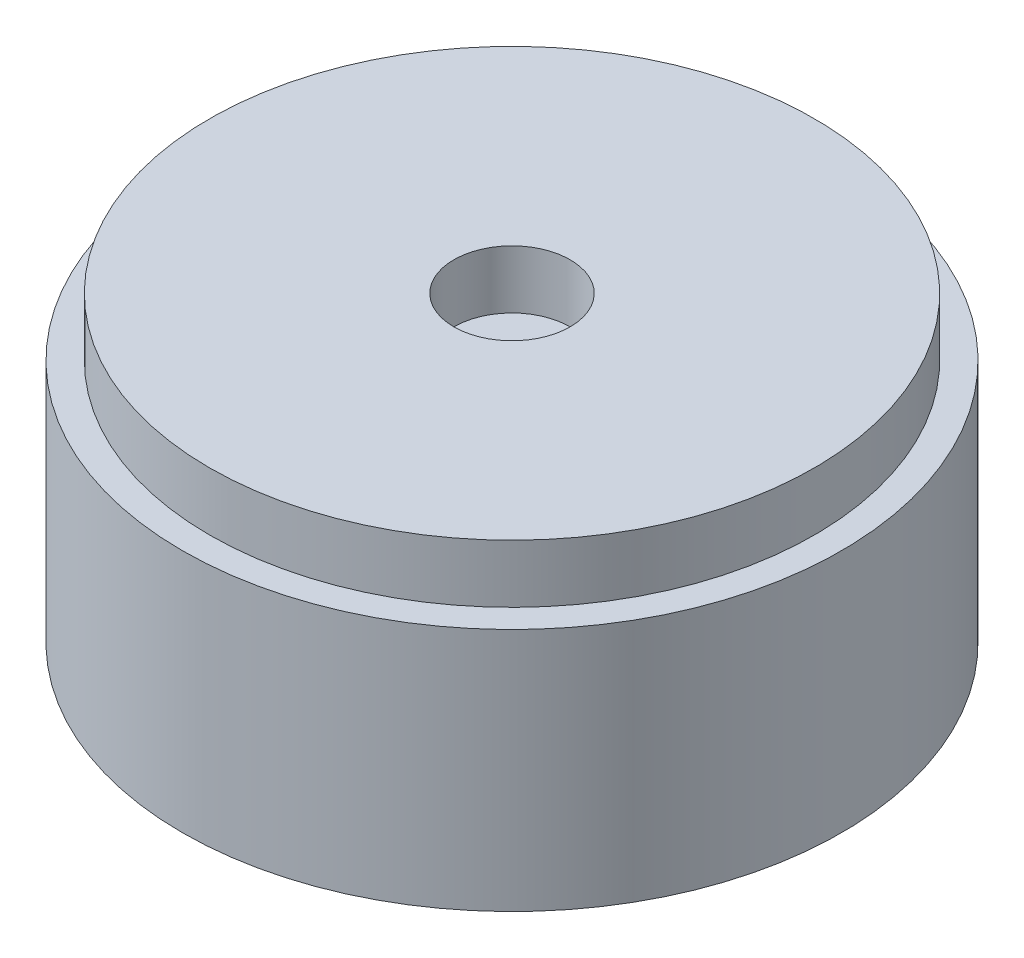
SolidWorks part; units mm, degrees
material "ABS"
ref_plane "Front Plane" through (0, 0, 0) normal (0, 0, 1) x (1, 0, 0)
ref_plane "Top Plane" through (0, 0, 0) normal (0, 1, 0) x (1, 0, 0)
ref_plane "Right Plane" through (0, 0, 0) normal (1, 0, 0) x (0, 0, -1)
sketch "Sketch1" plane through (0, 0, 0) normal (0, 1, 0) x (1, 0, 0)
  circle A0 centre (0, 0) radius 8.5
  dimension "D1" = 17
extrude "Boss-Extrude1" add sketch "Sketch1" along normal blind 7.8
sketch "Sketch2" plane through (0, 7.8, 0) normal (0, 1, 0) x (1, 0, 0)
  circle A1 centre (0, 0) radius 8.5
  circle A2 centre (0, 0) radius 8.5
  circle A3 centre (0, 0) radius 1.5
  circle A4 centre (0, 0) radius 7.8
  circle A5 centre (0, 0) radius 7.8
  circle M3 centre (0, 0) radius 8.5
  dimension "D3" = 3
  dimension "D1" = 0
  dimension "D2" = 0.7
extrude "Cut-Extrude1" cut sketch "Sketch2" against normal blind 1.5 contours A3 | A5 M3 region at (-8.2596, 7.8, 0) region at (0, 7.8, 0)
sketch "Sketch3" plane through (0, 0, 0) normal (0, -1, 0) x (1, 0, 0)
  line L0 (-5, 5) -> (5, -5) construction
  circle A0 centre (-5, 5) radius 0.5
  circle A1 centre (5, -5) radius 0.5
  point P4 (0, 0)
  dimension "D1" = 1
  dimension "D2" = 10
  dimension "D3" = 10
extrude "Boss-Extrude2" add sketch "Sketch3" along normal blind 2
chamfer "Chamfer1" distance 0.5 distance2 0.1 2 edges at (-5, -2, 4.5) (5, -2, -5.5) first distance on face at (-5, -2, 4.5) first distance on face at (5, -2, -5.5)
fillet "Fillet1" radius 1 2 edges at (-5, -1.5, 4.5) (5, -1.5, -5.5)
